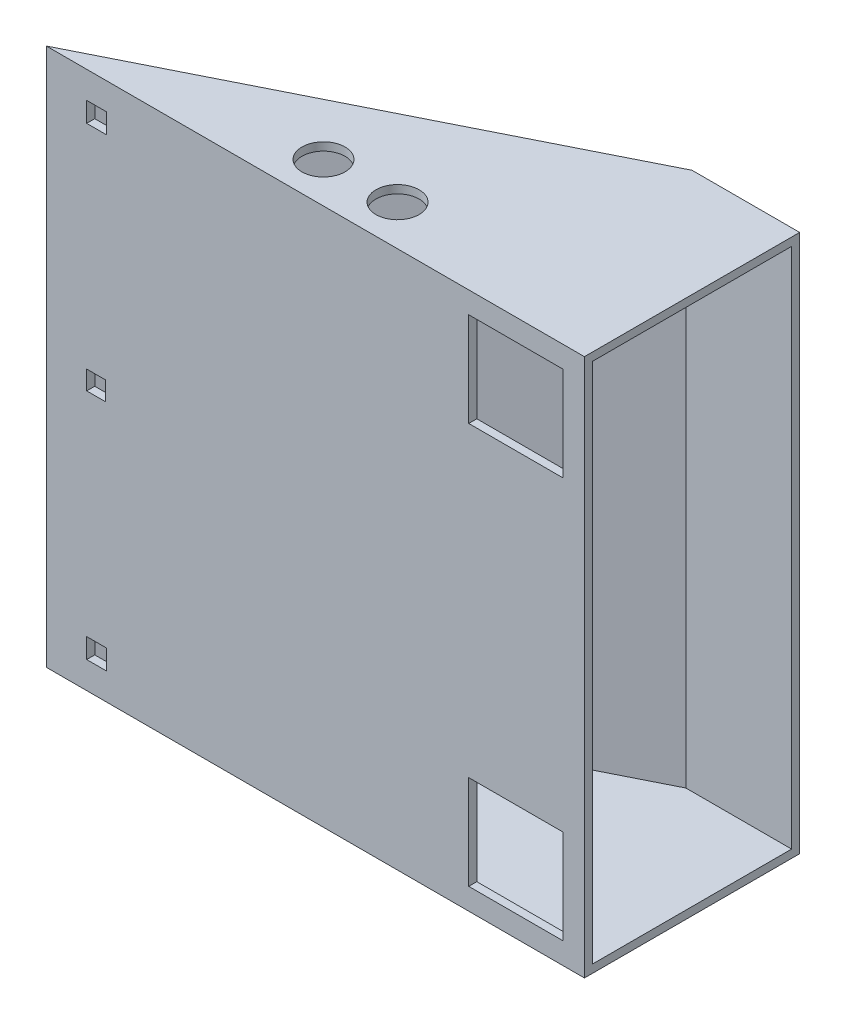
SolidWorks part; units mm, degrees
ref_plane "Alzado" through (0, 0, 0) normal (0, 0, 1) x (1, 0, 0)
ref_plane "Planta" through (0, 0, 0) normal (0, 1, 0) x (1, 0, 0)
ref_plane "Vista lateral" through (0, 0, 0) normal (1, 0, 0) x (0, 0, -1)
sketch "Croquis1" plane through (0, 0, 0) normal (0, 1, 0) x (1, 0, 0)
  line L0 (0, 0) -> (200, 0)
  line L5 (200, 0) -> (200, 80)
  line L6 (200, 80) -> (160, 80)
  line L7 (160, 80) -> (0, 0)
  dimension "D1" = 200
  dimension "D2" = 80
  dimension "D3" = 40
extrude "Saliente-Extruir2" add sketch "Croquis1" along normal blind 200
sketch "Croquis2" plane through (0, 200, 0) normal (0, 1, 0) x (1, 0, 0)
  line L0 (0, 0) -> (200, 0) construction
  circle A0 centre (88.0116, 15) radius 8.02
  circle A1 centre (115.5316, 15) radius 8.02
  dimension "D2" = 16.04
  dimension "D3" = 15
  dimension "D4" = 16.04
  dimension "D1" = 15
  dimension "D5" = 27.52
sketch "Croquis3" plane through (0, 0, -80) normal (0, 0, -1) x (-1, 0, 0)
  line L0 (-200, 0) -> (-200, 200) construction
sketch "Croquis5" plane through (0, 0, 0) normal (0, -1, 0) x (1, 0, 0)
  circle A0 centre (88.0116, -15) radius 8.02
  circle A1 centre (115.5316, -15) radius 8.02
ref_plane "Plano1" through (0, 0, 0) normal (1, 0, 0) x (0, 0, -1)
shell "Vaciado2" thickness 3 removed face at (200, 100, -40)
sketch "Croquis6" plane through (0, 0, 0) normal (1, 0, 0) x (0, 0, -1)
  line L1 (0, 200) -> (0, 0) construction
  line L3 (30, 88.575) -> (30, 111.425) construction
  line L4 (80, 0) -> (0, 0) construction
  circle A0 centre (30, 88.575) radius 8.2
  circle A1 centre (30, 111.425) radius 8.2
  point P2 (30, 100)
  dimension "D1" = 16.4
  dimension "D2" = 22.85
  dimension "D3" = 30
  dimension "D4" = 16.4
  dimension "D6" = 30
  dimension "D5" = 100
extrude "Cortar-Extruir4" cut sketch "Croquis6" along normal blind 80 contours A1 | A0
extrude "Cortar-Extruir5" cut sketch "Croquis2" against normal blind 3 contours A0 | A1
extrude "Cortar-Extruir6" cut sketch "Croquis5" against normal blind 3 contours A0 | A1
sketch "Croquis7" plane through (0, 0, 0) normal (0, 0, 1) x (1, 0, 0)
  line L0 (0, 0) -> (200, 0) construction
  line L1 (15, 10) -> (22.4, 10)
  line L2 (15, 10) -> (15, 17.4)
  line L3 (15, 17.4) -> (22.4, 17.4)
  line L4 (22.4, 10) -> (22.4, 17.4)
  line L5 (0, -44) -> (0, 44) construction
  point P4 (18.7, 10)
  dimension "D1" = 7.4
  dimension "D2" = 7.4
  dimension "D3" = 10
  dimension "D4" = 15
ref_plane "Plano2" through (0, 100, 0) normal (0, 1, 0) x (1, 0, 0)
extrude "Cortar-Extruir11" cut sketch "Croquis7" against normal blind 3 contours L4 L3 L2 L1
mirror "Simetría5" about plane through (0, 100, 0) normal (0, 1, 0) of "Cortar-Extruir11"
sketch "Croquis8" plane through (0, 0, 0) normal (0, 0, 1) x (1, 0, 0)
  line L0 (0, 200) -> (200, 200) construction
  line L1 (22.04, 103.52) -> (15, 103.52)
  line L2 (22.04, 103.52) -> (22.04, 96.48)
  line L3 (22.04, 96.48) -> (15, 96.48)
  line L4 (15, 103.52) -> (15, 96.48)
  line L5 (0, 0) -> (200, 0) construction
  line L7 (0, -44) -> (0, 44) construction
  point P6 (18.52, 103.52)
  point P9 (18.52, 96.48)
  dimension "D1" = 96.48
  dimension "D2" = 96.48
  dimension "D3" = 3.52
  dimension "D4" = 15
extrude "Cortar-Extruir12" cut sketch "Croquis8" against normal blind 3
sketch "Croquis9" plane through (0, 0, 0) normal (0, 0, 1) x (1, 0, 0)
  line L0 (200, 0) -> (200, 200) construction
  line L1 (192, 192) -> (157, 192)
  line L2 (192, 192) -> (192, 157)
  line L3 (192, 157) -> (157, 157)
  line L4 (157, 192) -> (157, 157)
  line L5 (0, 200) -> (200, 200) construction
  dimension "D1" = 8
  dimension "D2" = 8
  dimension "D3" = 35
  dimension "D4" = 35
extrude "Cortar-Extruir13" cut sketch "Croquis9" against normal blind 3
mirror "Simetría6" about plane through (0, 100, 0) normal (0, 1, 0) of "Cortar-Extruir13"
